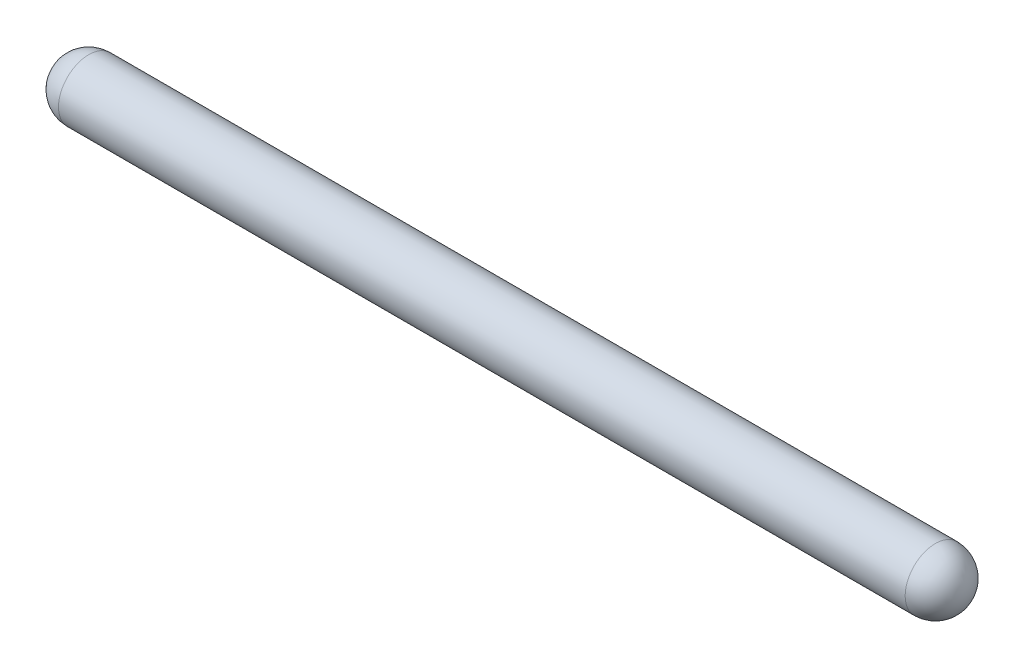
SolidWorks part; units mm, degrees
material "Plain Carbon Steel"
ref_plane "Front Plane" through (0, 0, 0) normal (0, 0, 1) x (1, 0, 0)
ref_plane "Top Plane" through (0, 0, 0) normal (0, 1, 0) x (1, 0, 0)
ref_plane "Right Plane" through (0, 0, 0) normal (1, 0, 0) x (0, 0, -1)
sketch "Sketch1" plane through (0, 0, 0) normal (0, 0, 1) x (1, 0, 0)
  line L0 (-14, 0) -> (14, 0)
  line L3 (14, 0) -> (14, 1)
  line L4 (14, 1) -> (-14, 1)
  line L5 (-14, 1) -> (-14, 0)
  point P4 (0, 0)
  dimension "D2" = 28
  dimension "D1" = 1
revolve "Revolve1" add sketch "Sketch1" angle 360 about L0
dome "Dome1" faces to dome 1 distance 1 reverse direction no elliptical dome no face at (-14, 0, 1) parameters "D1"=1
dome "Dome2" faces to dome 1 distance 1 face at (14, 0, 1) parameters "D1"=1
